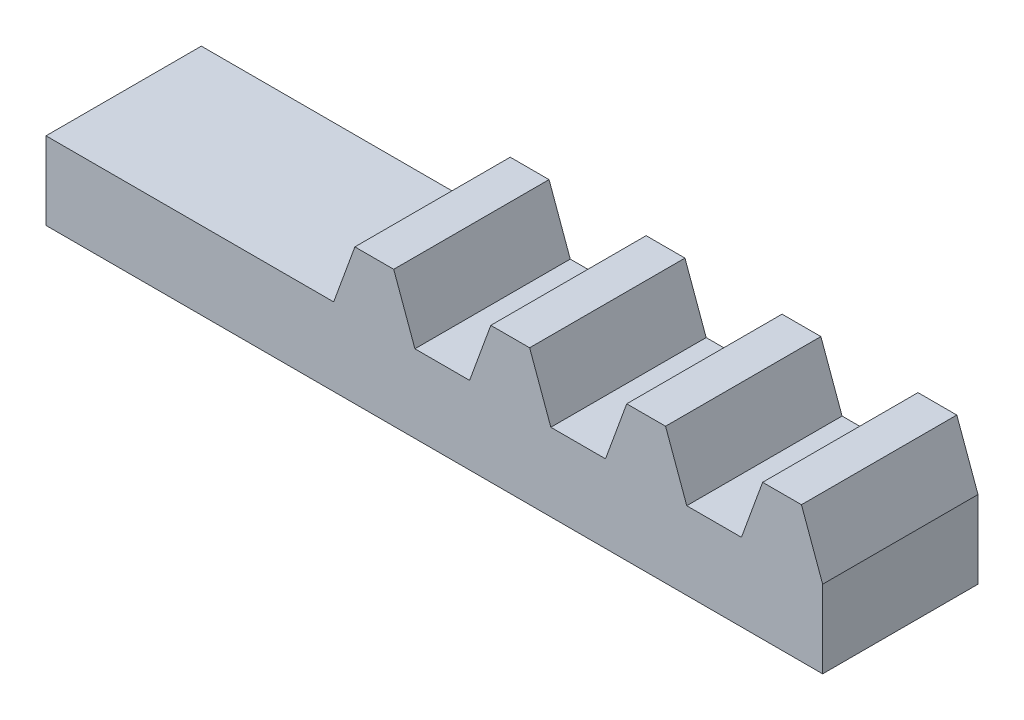
SolidWorks part; units mm, degrees
ref_plane "Front Plane" through (0, 0, 0) normal (0, 0, 1) x (1, 0, 0)
ref_plane "Top Plane" through (0, 0, 0) normal (0, 1, 0) x (1, 0, 0)
ref_plane "Right Plane" through (0, 0, 0) normal (1, 0, 0) x (0, 0, -1)
sketch "Sketch1" plane through (0, 0, 0) normal (0, 0, 1) x (1, 0, 0)
  line L0 (10, 1) -> (9.454, 2.5)
  line L1 (-10, -1) -> (10, -1)
  line L2 (-10, -1) -> (-10, 1)
  line L3 (-10, 1) -> (-2.5919, 1)
  line L4 (10, -1) -> (10, 1)
  line L7 (9.454, 2.5) -> (8.454, 2.5)
  line L8 (8.454, 2.5) -> (7.9081, 1)
  line L9 (6.5, 1) -> (5.954, 2.5)
  line L10 (5.954, 2.5) -> (4.954, 2.5)
  line L11 (4.954, 2.5) -> (4.4081, 1)
  line L12 (-13.5, 1) -> (-2.5919, 1)
  line L13 (3, 1) -> (2.454, 2.5)
  line L14 (2.454, 2.5) -> (1.454, 2.5)
  line L15 (1.454, 2.5) -> (0.9081, 1)
  line L16 (-17, 1) -> (-2.5919, 1)
  line L17 (-0.5, 1) -> (-1.046, 2.5)
  line L18 (-1.046, 2.5) -> (-2.046, 2.5)
  line L19 (-2.046, 2.5) -> (-2.5919, 1)
  line L20 (-20.5, 1) -> (-2.5919, 1)
  line L21 (-0.5, 1) -> (0.9081, 1)
  line L22 (-0.5, 1) -> (0.9081, 1)
  line L23 (-0.5, 1) -> (0.9081, 1)
  line L24 (3, 1) -> (4.4081, 1)
  line L25 (3, 1) -> (4.4081, 1)
  line L26 (6.5, 1) -> (7.9081, 1)
  point P0 (0, 0)
  dimension "D1" = 2
  dimension "D2" = 20
  dimension "D3" = 1
  dimension "D4" = 110
  dimension "D5" = 110
  dimension "D6" = 1.5
  dimension "D7" = 4
extrude "Boss-Extrude1" add sketch "Sketch1" along normal blind 4 contours L26 L9 L10 L11 L24 L13 L14 L15 L21 L17 L18 L19 L3 L2 L1 L4 L0 L7 L8 region at (0.6973, 0.3128, 0)
